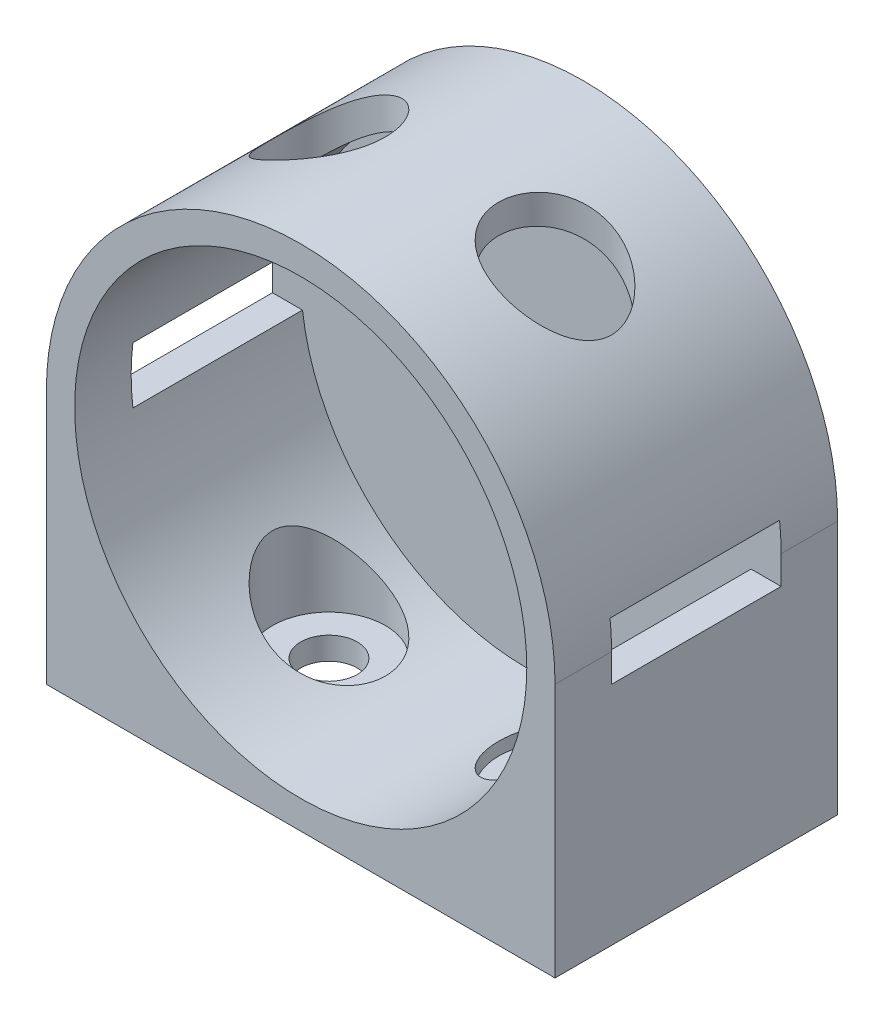
SolidWorks part; units mm, degrees
ref_plane "Front Plane" through (0, 0, 0) normal (0, 0, 1) x (1, 0, 0)
ref_plane "Top Plane" through (0, 0, 0) normal (0, 1, 0) x (1, 0, 0)
ref_plane "Right Plane" through (0, 0, 0) normal (1, 0, 0) x (0, 0, -1)
sketch "Sketch2" plane through (0, 0, 0) normal (0, 0, 1) x (1, 0, 0)
  circle A1 centre (0, 0) radius 22.5
  dimension "D2" = 45
extrude "Boss-Extrude3" add sketch "Sketch2" along normal blind 25
sketch "Sketch6" plane through (0, 0, 0) normal (0, 0, 1) x (1, 0, 0)
  line L1 (-22.5, 0) -> (22.5, 0)
  line L2 (-22.5, 0) -> (-22.5, -22.5)
  line L3 (-22.5, -22.5) -> (22.5, -22.5)
  line L4 (22.5, 0) -> (22.5, -22.5)
  circle A0 centre (0, 0) radius 22.5 construction
extrude "Boss-Extrude4" add sketch "Sketch6" along normal blind 25
sketch "Sketch4" plane through (0, 0, 25) normal (0, 0, 1) x (1, 0, 0)
  circle A0 centre (0, 0) radius 20
  dimension "D1" = 40
extrude "Cut-Extrude1" cut sketch "Sketch4" against normal blind 20
sketch "Sketch5" plane through (0, 0, 0) normal (0, 0, -1) x (-1, 0, 0)
  circle A0 centre (0, 0) radius 2.5
  dimension "D1" = 5
extrude "Cut-Extrude2" cut sketch "Sketch5" against normal up to surface (5 mm away) up to face at (20, 0, 5)
sketch "Sketch7" plane through (0, -22.5, 0) normal (0, -1, 0) x (1, 0, 0)
  line L0 (0, 25) -> (0, 0) construction
  line L1 (-22.5, 25) -> (22.5, 25) construction
  circle A3 centre (-10, 12.5) radius 5
  circle A4 centre (10, 12.5) radius 5
  point P9 (0, 12.5)
  dimension "D2" = 10
  dimension "D4" = 10
extrude "Cut-Extrude6" cut sketch "Sketch7" against normal through all
sketch "Sketch9" plane through (0, -22.5, 0) normal (0, -1, 0) x (1, 0, 0)
  line L0 (0, 25) -> (0, 0) construction
  line L1 (-22.5, 25) -> (22.5, 25) construction
  circle A0 centre (-10, 12.5) radius 5
  circle A1 centre (-10, 12.5) radius 2.5
  circle A2 centre (10, 12.5) radius 2.5
  circle A3 centre (10, 12.5) radius 5
  dimension "D1" = 10
  dimension "D2" = 5
extrude "Boss-Extrude5" add sketch "Sketch9" against normal blind 2
sketch "Sketch14" plane through (22.5, 0, 0) normal (1, 0, 0) x (0, 0, -1)
  line L0 (-25, 0) -> (0, 0) construction
  line L1 (-20, 0) -> (-5, 0)
  line L2 (-20, 2.5) -> (-20, -2.5)
  line L3 (-20, -2.5) -> (-5, -2.5)
  line L4 (-5, 2.5) -> (-5, -2.5)
  line L5 (0, -22.5) -> (0, 0) construction
  line L6 (-25, -22.5) -> (-25, 0) construction
  line L7 (-20, 2.5) -> (-5, 2.5)
  dimension "D1" = 5
  dimension "D2" = 5
  dimension "D3" = 2.5
extrude "Cut-Extrude8" cut sketch "Sketch14" against normal through all contours L7 L4 L3 L2
